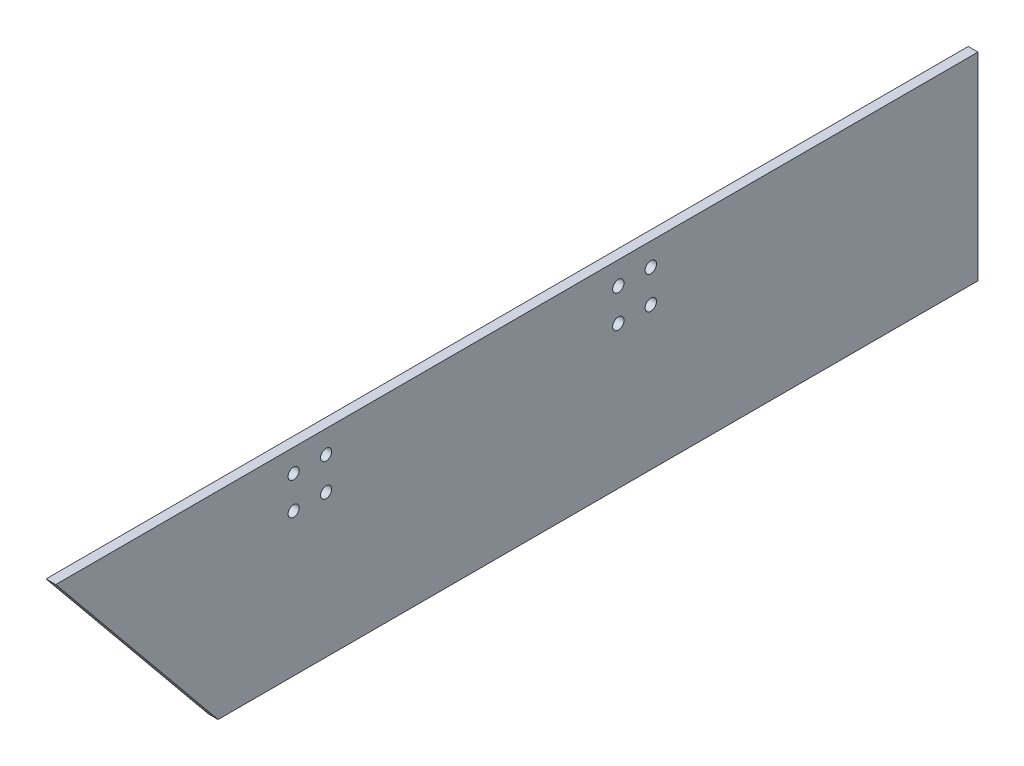
SolidWorks part; units mm, degrees
ref_plane "Front Plane" through (0, 0, 0) normal (0, 0, 1) x (1, 0, 0)
ref_plane "Top Plane" through (0, 0, 0) normal (0, 1, 0) x (1, 0, 0)
ref_plane "Right Plane" through (0, 0, 0) normal (1, 0, 0) x (0, 0, -1)
sketch "Sketch1" plane through (0, 0, 0) normal (0, 0, 1) x (1, 0, 0)
  line L0 (3, 76) -> (3, 0)
  line L2 (0, 0) -> (0, 76)
  line L5 (3, 0) -> (0, 0)
  line L6 (3, 76) -> (0, 76)
  dimension "D1" = 76
  dimension "D2" = 3
extrude "Boss-Extrude1" add sketch "Sketch1" along normal blind 220 contours L2 L0 region at (1.5, 38, 0)
hole_wizard "M3 Clearance Hole1" positions "Sketch2" profile "Sketch3" hole size "M3" standard "ANSI Metric" end condition through all
sketch "Sketch2" plane through (0, 0, 0) normal (-1, 0, 0) x (0, 0, 1)
  point P0 (50.7547, 59)
  point P3 (60.7547, 59)
  point P6 (60.7547, 69)
  point P9 (50.7547, 69)
  point P12 (200.7547, 59)
  point P15 (200.7547, 69)
  point P18 (210.7547, 59)
  point P21 (210.7547, 69)
sketch "Sketch3" plane through (0, 59, 50.7547) normal (0, 1, 0) x (0, 0, 1)
  line L0 (0, 0) -> (0, 3)
  line L1 (0, 3) -> (1.7, 3)
  line L2 (1.7, 3) -> (1.7, 0.025)
  line L3 (1.7, 0.025) -> (1.725, 0)
  line L5 (1.725, 0) -> (0, 0)
  line L6 (-1.7, 0.025) -> (-1.725, 0) construction
  line L11 (0, -6.35) -> (0, 107.95) construction
  dimension "Thru Hole Dia." = 3.4
  dimension "Thru Hole Depth" = 3
  dimension "Near C'Sink Dia." = 3.45
  dimension "Near C'Sink Angle" = 90
sketch "Sketch4" plane through (0, 0, 0) normal (-1, 0, 0) x (0, 0, 1)
  line L0 (220, 0) -> (220, 76) construction
  line L1 (0, 0) -> (220, 0)
  line L2 (0, 0) -> (0, 15)
  line L3 (0, 15) -> (220, 15)
  line L4 (220, 0) -> (220, 15)
  dimension "D1" = 15
extrude "Cut-Extrude1" cut sketch "Sketch4" against normal through all
sketch "Sketch5" plane through (0, 0, 0) normal (-1, 0, 0) x (0, 0, 1)
  line L0 (200.7547, 69) -> (110.7547, 69) construction
  line L2 (110.7547, 69) -> (100.7547, 69) construction
  line L3 (110.7547, 69) -> (110.7547, 59) construction
  line L4 (110.7547, 59) -> (100.7547, 59) construction
  line L5 (100.7547, 69) -> (100.7547, 59) construction
  circle A0 centre (200.7547, 69) radius 1.725 construction
  circle A1 centre (200.7547, 69) radius 1.725 construction
  circle A2 centre (110.7547, 69) radius 1.75
  circle A4 centre (100.7547, 69) radius 1.75
  circle A5 centre (100.7547, 59) radius 1.75
  circle A6 centre (110.7547, 59) radius 1.75
  dimension "D2" = 3.5
  dimension "D1" = 90
  dimension "D3" = 10
  dimension "D4" = 10
extrude "Cut-Extrude2" cut sketch "Sketch5" against normal through all
sketch "Sketch6" plane through (0, 0, 0) normal (-1, 0, 0) x (0, 0, 1)
  circle A0 centre (50.7547, 59) radius 1.725 construction
  circle A1 centre (60.7547, 59) radius 1.7 construction
  circle A2 centre (60.7547, 69) radius 1.725 construction
  circle A3 centre (50.7547, 69) radius 1.725 construction
  circle A4 centre (50.7547, 59) radius 1.725
  circle A5 centre (60.7547, 59) radius 1.7
  circle A6 centre (60.7547, 69) radius 1.725
  circle A7 centre (50.7547, 69) radius 1.725
extrude "Boss-Extrude2" add sketch "Sketch6" against normal blind 3
sketch "Sketch8" plane through (0, 0, 0) normal (-1, 0, 0) x (0, 0, 1)
  line L0 (220, 15) -> (234, 15)
  line L1 (234, 15) -> (284, 76)
  line L2 (284, 76) -> (220, 76)
  line L3 (220, 15) -> (220, 76) construction
  line L4 (220, 76) -> (220, 15)
  dimension "D1" = 14
  dimension "D2" = 64
extrude "Boss-Extrude3" add sketch "Sketch8" against normal blind 3 contours L2 L4 L0 L1
